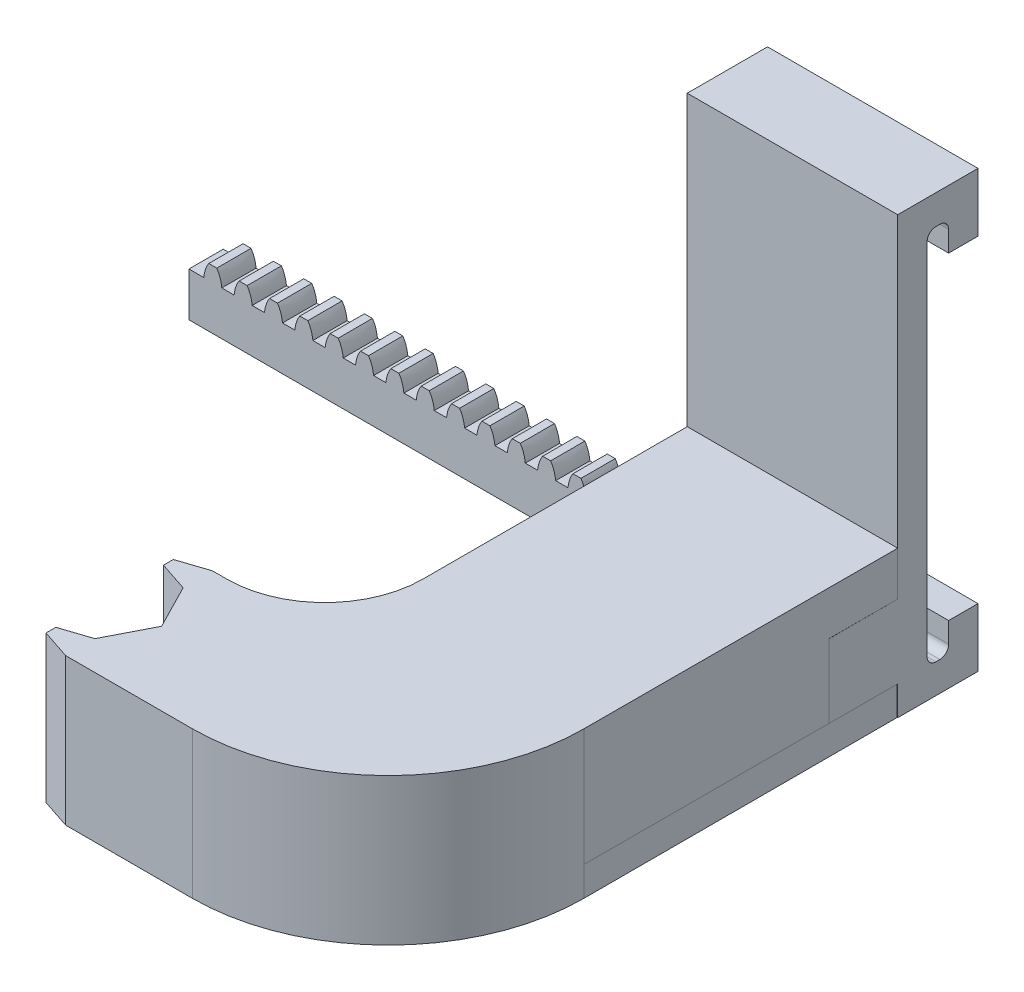
SolidWorks part; units mm, degrees
ref_plane "Vorne" through (0, 0, 0) normal (0, 0, 1) x (1, 0, 0)
ref_plane "Oben" through (0, 0, 0) normal (0, 1, 0) x (1, 0, 0)
ref_plane "Rechts" through (0, 0, 0) normal (1, 0, 0) x (0, 0, -1)
sketch "Skizze1" plane through (0, 0, 0) normal (0, 1, 0) x (1, 0, 0)
  line L0 (30.6398, 31.6347) -> (30.6398, -23.3653)
  line L3 (9.171, 31.6347) -> (30.6398, 31.6347)
  line L5 (30.6398, -23.3653) -> (-2.3602, -23.3653)
  line L7 (-2.3041, -8.3654) -> (9.171, -8.3654)
  line L8 (9.171, -8.3654) -> (9.171, 31.6347)
  line L9 (-2.3041, -8.3654) -> (-5.3106, -9.3654)
  line L10 (-5.3106, -9.3654) -> (-5.3106, -10.3654)
  line L11 (-5.3106, -10.3654) -> (-2.3041, -11.3654)
  line L12 (-5.3106, -13.3654) -> (-2.3041, -14.3654)
  line L13 (-5.3106, -12.3654) -> (-5.3106, -13.3654)
  line L14 (-2.3041, -11.3654) -> (-5.3106, -12.3654)
  line L15 (-5.3106, -16.3654) -> (-2.3041, -17.3654)
  line L16 (-5.3106, -15.3654) -> (-5.3106, -16.3654)
  line L17 (-2.3041, -14.3654) -> (-5.3106, -15.3654)
  line L18 (-5.3106, -19.3653) -> (-2.3041, -20.3653)
  line L19 (-5.3106, -18.3653) -> (-5.3106, -19.3653)
  line L20 (-2.3041, -17.3654) -> (-5.3106, -18.3653)
  line L21 (-5.3106, -22.3653) -> (-2.3041, -23.3653)
  line L22 (-5.3106, -21.3653) -> (-5.3106, -22.3653)
  line L23 (-2.3041, -20.3653) -> (-5.3106, -21.3653)
  point P0 (-5.3041, -8.3654)
  dimension "D2" = 33
  dimension "D1" = 55
  dimension "D3" = 21.4688
  dimension "D4" = 15
  dimension "D5" = 3
  dimension "D6" = 1
  dimension "D7" = 0
  dimension "D8" = 1
  dimension "D9" = 1
  dimension "D10" = 5
extrude "Aufsatz-Linear austragen1" add sketch "Skizze1" along normal blind 3 contours L3 region at (17.3452, 0, -1.2107)
sketch "Skizze2" plane through (0, 0, -31.6347) normal (0, 0, -1) x (-1, 0, 0)
  line L2 (-30.6894, 7) -> (-30.6894, 44.5)
  line L3 (-30.6894, 44.5) -> (-9.1904, 44.5)
  line L4 (-9.1904, 17) -> (-9.1904, 44.5)
  line L6 (-30.6894, 7) -> (-30.6894, 0)
  line L7 (-30.6894, 0) -> (-9.1904, 0)
  line L8 (-9.1904, 17) -> (-9.1904, 0)
  line L9 (-9.171, 3) -> (-30.6398, 3) construction
  dimension "D1" = 44.5
  dimension "D2" = 3
extrude "Aufsatz-Linear austragen2" add sketch "Skizze2" against normal blind 3
sketch "Skizze3" plane through (30.6894, 0, 0) normal (1, 0, 0) x (0, 0, -1)
  line L4 (36.8347, 44.5) -> (36.8347, 41.5)
  line L6 (36.8347, 41.5) -> (36.8347, 38.5)
  line L7 (36.8347, 38.5) -> (33.8347, 38.5)
  line L8 (33.8347, 40.6) -> (33.8347, 38.5)
  line L12 (36.8347, 0) -> (36.8347, 3)
  line L14 (36.8347, 3) -> (36.8347, 6)
  line L15 (36.8347, 6) -> (33.8347, 6)
  line L16 (33.8347, 3.9) -> (33.8347, 6)
  line L19 (28.6347, 44.5) -> (28.6347, 0) construction
  line L21 (31.6347, 38.5) -> (31.6347, 40.6)
  line L22 (31.6347, 38.5) -> (28.6347, 38.5)
  line L23 (28.6347, 44.5) -> (28.6347, 0) construction
  line L25 (32.5347, 3) -> (32.9347, 3)
  line L26 (32.5347, 41.5) -> (32.9347, 41.5)
  line L27 (36.8347, 44.5) -> (28.6347, 44.5)
  line L28 (28.6347, 44.5) -> (28.6347, 38.5)
  line L30 (31.6347, 3.9) -> (31.6347, 6)
  line L31 (31.6347, 6) -> (28.6347, 6)
  line L32 (28.6347, 6) -> (28.6347, 0)
  line L33 (36.8347, 0) -> (28.6347, 0)
  arc A4 (33.8347, 40.6) -> (32.9347, 41.5) centre (32.9347, 40.6) ccw
  arc A5 (31.6347, 40.6) -> (32.5347, 41.5) centre (32.5347, 40.6) cw
  arc A6 (33.8347, 3.9) -> (32.9347, 3) centre (32.9347, 3.9) cw
  arc A7 (31.6347, 3.9) -> (32.5347, 3) centre (32.5347, 3.9) ccw
  dimension "D9" = 3
  dimension "D11" = 0.9
  dimension "D1" = 3
  dimension "D2" = 6
  dimension "D3" = 3
  dimension "D4" = 3
  dimension "D5" = 3
  dimension "D6" = 8.2
  dimension "D7" = 3
  dimension "D8" = 3
  dimension "D10" = 3
  dimension "D12" = 3
  dimension "D13" = 0.4
  dimension "D14" = 8.2
  dimension "D15" = 3
  dimension "D16" = 0
extrude "Aufsatz-Linear austragen3" add sketch "Skizze3" against normal up to surface (21.499 mm away) up to face at (9.1904, 23.75, -30.1347)
sketch "Skizze4" plane through (0, 0, -28.6347) normal (0, 0, 1) x (1, 0, 0)
  line L5 (9.2206, 10.5) -> (-34.71, 10.5)
  line L7 (9.2206, 7) -> (-34.71, 7)
  line L8 (-34.71, 10.5) -> (-34.71, 7)
  line L13 (30.6894, 0) -> (30.6398, 0) construction
  line L14 (9.2206, 10.5) -> (11.7031, 10.5)
  line L16 (9.2206, 7) -> (11.7031, 7)
  line L18 (30.6894, 44.5) -> (30.6894, 0) construction
  line L19 (11.7031, 10.5) -> (30.6894, 10.5)
  line L21 (11.7031, 7) -> (30.6894, 7)
  line L22 (30.6894, 10.5) -> (30.6894, 7)
  dimension "D1" = 3.5
  dimension "D2" = 10.5
extrude "Aufsatz-Linear austragen4" add sketch "Skizze4" along normal blind 7
sketch "Skizze5" plane through (0, 0, -21.6347) normal (0, 0, 1) x (1, 0, 0)
  line L0 (8.9471, 10.5) -> (7.1052, 10.5)
  line L1 (7.6184, 12) -> (8.4339, 12)
  line L27 (30.6894, 10.5) -> (-34.71, 10.5) construction
  spline S0 degree 2 poles (7.6184, 12) (7.2013, 11.3915) (7.1052, 10.5) knots 0 0 0 1 1 1
  spline S1 degree 2 poles (8.4339, 12) (8.8511, 11.3915) (8.9471, 10.5) knots 0 0 0 1 1 1
  point P4 (8.0262, 3)
  point P5 (8.0262, 4.4523)
  dimension "D1" = 0
  dimension "D2" = 1.5
extrude "Aufsatz-Linear austragen5" add sketch "Skizze5" against normal blind 7 contours L0 S0 L1 S1
pattern_linear "Lineares Muster1" count 14 spacing 3.1 along (-1, 0, 0) count 8 spacing 3.1 along (1, 0, 0) of "Aufsatz-Linear austragen5"
sketch "Skizze6" plane through (0, 0, -21.6347) normal (0, 0, 1) x (1, 0, 0)
  line L0 (30.6894, 7) -> (30.6894, 0) construction
  line L1 (9.1904, 7) -> (30.6894, 7)
  line L2 (9.1904, 7) -> (9.1904, 3)
  line L3 (9.1904, 3) -> (30.6894, 3)
  line L4 (30.6894, 7) -> (30.6894, 3)
  line L5 (30.6398, 3) -> (9.1904, 3) construction
  dimension "D1" = 0
  dimension "D2" = 0
extrude "Aufsatz-Linear austragen6" add sketch "Skizze6" against normal up to surface (7 mm away) up to face at (23.5065, 3.3333, -28.6347)
fillet "Verrundung1" radius 20 1 edges at (30.6398, 1.5, 23.3653)
fillet "Verrundung2" radius 10 1 edges at (9.171, 1.5, 8.3654)
sketch "Skizze7" plane through (-34.71, 0, 0) normal (-1, 0, 0) x (0, 0, 1)
  line L0 (-28.6347, 12) -> (-21.6347, 12) construction
  line L1 (-28.6347, 7) -> (-25.1347, 7)
  line L2 (-28.6347, 7) -> (-28.6347, 12)
  line L3 (-28.6347, 12) -> (-25.1347, 12)
  line L4 (-25.1347, 7) -> (-25.1347, 12)
extrude "Schnitt-Linear austragen1" cut sketch "Skizze7" against normal up to surface (43.9005 mm away) up to face at (9.1904, 18.4048, -31.8728)
sketch "Skizze8" plane through (-34.71, 0, 0) normal (-1, 0, 0) x (0, 0, 1)
  line L0 (-21.6347, 7) -> (-21.6347, 3) construction
  line L1 (-25.1347, 7) -> (-21.6347, 7)
  line L2 (-25.1347, 7) -> (-25.1347, 6)
  line L3 (-25.1347, 6) -> (-21.6347, 6)
  line L4 (-21.6347, 7) -> (-21.6347, 6)
  dimension "D1" = 1
extrude "Aufsatz-Linear austragen7" add sketch "Skizze8" against normal up to surface (43.9005 mm away) up to face at (9.1904, 18.0455, -31.4074)
sketch "Skizze9" plane through (0, 3, 0) normal (0, 1, 0) x (1, 0, 0)
  line L0 (9.171, 1.6346) -> (9.1904, 28.6347)
  line L1 (9.1904, 28.6347) -> (30.6894, 28.6347)
  line L2 (30.6894, 28.6347) -> (30.6398, -3.3653)
  line L3 (10.6398, -23.3653) -> (-2.3041, -23.3653)
  line L4 (-2.3041, -23.3653) -> (-5.3106, -22.3653)
  line L5 (-5.3106, -22.3653) -> (-5.3106, -21.3653)
  line L6 (-5.3106, -21.3653) -> (-2.3041, -20.3653)
  line L7 (-2.3041, -20.3653) -> (-5.3106, -19.3653)
  line L8 (-5.3106, -19.3653) -> (-5.3106, -18.3653)
  line L10 (-5.3106, -18.3653) -> (-2.3041, -17.3654)
  line L11 (-2.3041, -17.3654) -> (-5.3106, -16.3654)
  line L12 (-5.3106, -16.3654) -> (-5.3106, -15.3654)
  line L13 (-5.3106, -15.3654) -> (-2.3041, -14.3654)
  line L14 (-2.3041, -14.3654) -> (-5.3106, -13.3654)
  line L15 (-5.3106, -13.3654) -> (-5.3106, -12.3654)
  line L16 (-5.3106, -12.3654) -> (-2.3041, -11.3654)
  line L17 (-2.3041, -11.3654) -> (-5.3106, -10.3654)
  line L18 (-5.3106, -10.3654) -> (-5.3106, -9.3654)
  line L19 (-5.3106, -9.3654) -> (-2.3041, -8.3654)
  line L20 (-2.3041, -8.3654) -> (-0.829, -8.3654)
  arc A0 (10.6398, -23.3653) -> (30.6398, -3.3653) centre (10.6398, -3.3653) ccw
  arc A1 (-0.829, -8.3654) -> (9.171, 1.6346) centre (-0.829, 1.6346) ccw
  point P17 (-5.3106, -18.8653)
  point P27 (-5.3106, -18.3653)
extrude "Aufsatz-Linear austragen8" add sketch "Skizze9" along normal blind 12
sketch "Skizze10" plane through (0, 15, 0) normal (0, 1, 0) x (1, 0, 0)
  line L0 (-2.3041, -11.3654) -> (0, -15.8654)
  line L1 (0, -15.8654) -> (-2.3041, -20.3653)
  line L2 (-2.3041, -20.3653) -> (-8.1518, -20.3653)
  line L3 (-8.1518, -20.3653) -> (-8.1518, -11.3654)
  line L4 (-8.1518, -11.3654) -> (-2.3041, -11.3654)
extrude "Schnitt-Linear austragen2" cut sketch "Skizze10" against normal blind 22.95
